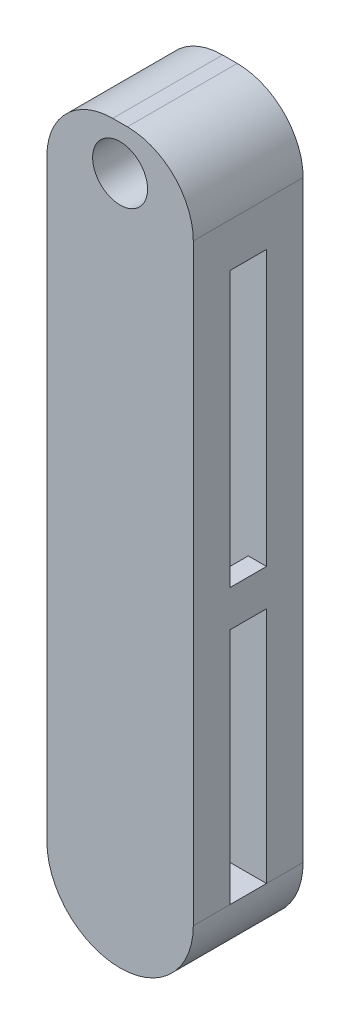
SolidWorks part; units mm, degrees
material "ABS"
ref_plane "Front" through (0, 0, 0) normal (0, 0, 1) x (1, 0, 0)
ref_plane "Top" through (0, 0, 0) normal (0, 1, 0) x (1, 0, 0)
ref_plane "Right" through (0, 0, 0) normal (1, 0, 0) x (0, 0, -1)
sketch "Sketch2" plane through (0, 0, 0) normal (0, 0, 1) x (1, 0, 0)
  line L1 (-20, -100) -> (20, -100)
  line L2 (-20, -100) -> (-20, 100)
  line L3 (-20, 100) -> (20, 100)
  line L4 (20, -100) -> (20, 100)
  line L5 (-20, -100) -> (20, 100) construction
  line L6 (-20, 100) -> (20, -100) construction
  point P1 (0, 0)
  dimension "D1" = 200
  dimension "D2" = 40
extrude "Boss-Extrude1" add sketch "Sketch2" along normal blind 30
sketch "Sketch3" plane through (0, 0, 0) normal (0, 0, -1) x (-1, 0, 0)
  line L0 (20, -100) -> (-20, -100) construction
  circle A0 centre (0, -90) radius 2
  dimension "D1" = 4
  dimension "D2" = 10
extrude "Cut-Extrude1" cut sketch "Sketch3" against normal blind 10
fillet "Fillet1" radius 20 2 edges at (20, -100, 15) (-20, -100, 15)
sketch "Sketch5" plane through (0, 0, 30) normal (0, 0, 1) x (1, 0, 0)
  line L0 (20, -80) -> (20, 100) construction
  line L1 (20, 100) -> (-20, 100) construction
  circle A0 centre (0, 88) radius 7.5
  dimension "D1" = 15
  dimension "D2" = 20
  dimension "D3" = 12
extrude "Cut-Extrude3" cut sketch "Sketch5" against normal blind 20
fillet "Fillet2" radius 18 2 edges at (20, 100, 15) (-20, 100, 15)
sketch "Sketch6" plane through (-20, 0, 0) normal (-1, 0, 0) x (0, 0, 1)
  line L0 (0, -80) -> (30, -80) construction
  line L1 (10, -80) -> (20, -80)
  line L2 (10, -80) -> (10, 70)
  line L3 (10, 70) -> (20, 70)
  line L4 (20, -80) -> (20, 70)
  line L6 (20, 70) -> (30, 70) construction
  line L7 (10, 70) -> (0, 70) construction
  dimension "D1" = 10
  dimension "D2" = 150
extrude "Cut-Extrude4" cut sketch "Sketch6" against normal through all
sketch "Sketch7" plane through (0, 0, 20) normal (0, 0, -1) x (-1, 0, 0)
  line L0 (20, -80) -> (20, 70) construction
  line L2 (20, -5) -> (15, -5)
  line L3 (20, -5) -> (20, -15)
  line L4 (20, -15) -> (15, -15)
  line L5 (15, -5) -> (15, -15)
  dimension "D1" = 5
  dimension "D2" = 10
extrude "Boss-Extrude2" add sketch "Sketch7" along normal blind 15
mirror "Mirror1" about plane through (0, 0, 0) normal (1, 0, 0) of "Boss-Extrude2"
